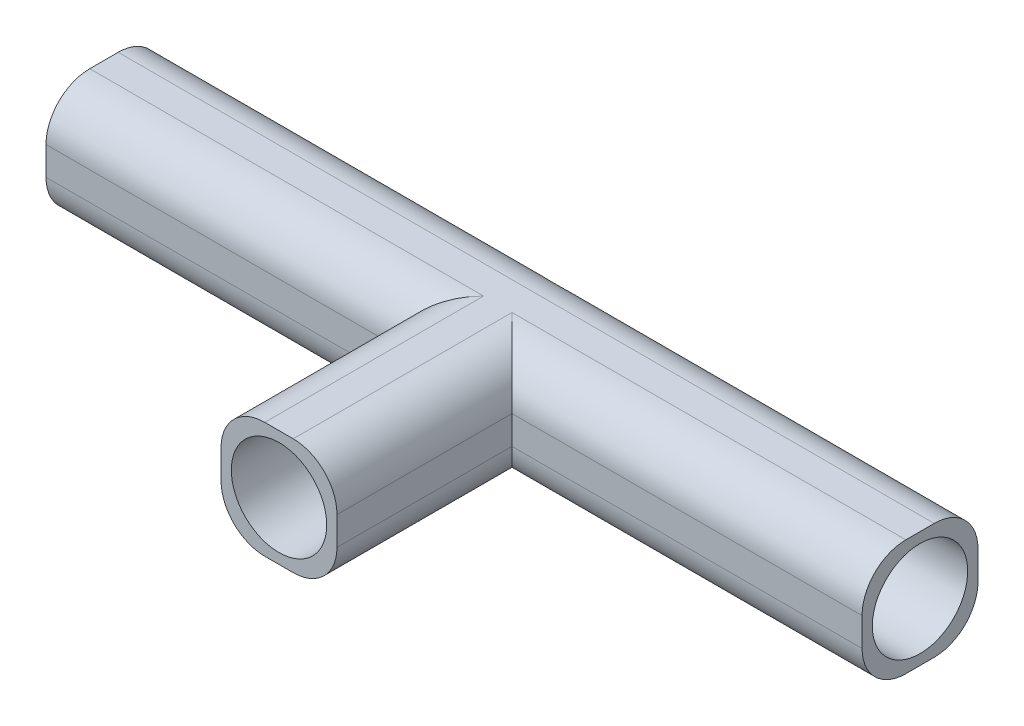
SolidWorks part; units mm, degrees
ref_plane "Front Plane" through (0, 0, 0) normal (0, 0, 1) x (1, 0, 0)
ref_plane "Top Plane" through (0, 0, 0) normal (0, 1, 0) x (1, 0, 0)
ref_plane "Right Plane" through (0, 0, 0) normal (1, 0, 0) x (0, 0, -1)
sketch "Sketch2" plane through (0, 0, 0) normal (0, 1, 0) x (1, 0, 0)
  line L0 (0, 0) -> (0, 66.5)
  line L1 (0, 66.5) -> (106.5, 66.5)
  line L2 (106.5, 66.5) -> (106.5, 40)
  line L3 (106.5, 40) -> (26.5, 40)
  line L4 (26.5, 40) -> (26.5, 0)
  line L5 (26.5, 0) -> (0, 0)
  dimension "D1" = 40
  dimension "D2" = 26.5
  dimension "D3" = 80
extrude "Boss-Extrude1" add sketch "Sketch2" along normal blind 26.5
sketch "Sketch3" plane through (0, 0, 0) normal (0, 0, 1) x (1, 0, 0)
  line L0 (0, 0) -> (26.5, 26.5) construction
  circle A0 centre (13.25, 13.25) radius 10.9
  dimension "D1" = 21.8
extrude "Cut-Extrude1" cut sketch "Sketch3" against normal through all
sketch "Sketch6" plane through (0, 0, 0) normal (-1, 0, 0) x (0, 0, 1)
  line L0 (-66.5, 0) -> (0, 0) construction
  line L1 (-66.5, 26.5) -> (-40, 26.5)
  line L2 (-66.5, 26.5) -> (-66.5, 0)
  line L3 (-66.5, 0) -> (-40, 0)
  line L4 (-40, 26.5) -> (-40, 0)
extrude "Boss-Extrude3" add sketch "Sketch6" along normal blind 80
sketch "Sketch7" plane through (-80, 0, 0) normal (-1, 0, 0) x (0, 0, 1)
  line L0 (-66.5, 26.5) -> (-40, 0) construction
  circle A0 centre (-53.25, 13.25) radius 10.9
  dimension "D1" = 21.8
extrude "Cut-Extrude2" cut sketch "Sketch7" against normal through all
fillet "Fillet1" radius 10 10 edges at (0, 26.5, -20) (26.5, 26.5, -20) (0, 0, -20) (26.5, 0, -20) (66.5, 0, -40) (66.5, 26.5, -40) (-40, 26.5, -40) (13.25, 26.5, -66.5) (13.25, 0, -66.5) (-40, 0, -40)
